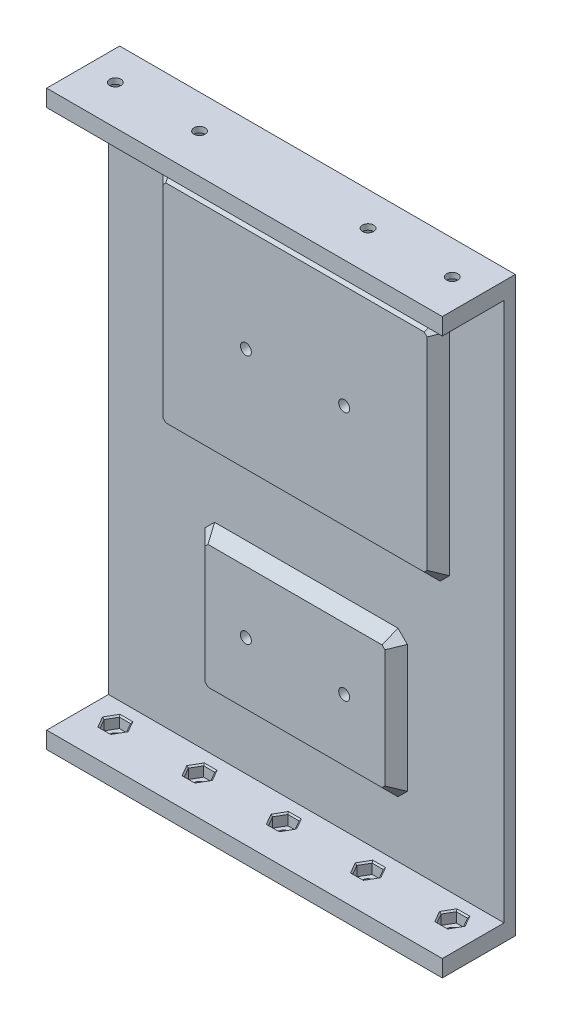
SolidWorks part; units mm, degrees
ref_plane "Front Plane" through (0, 0, 0) normal (0, 0, 1) x (1, 0, 0)
ref_plane "Top Plane" through (0, 0, 0) normal (0, 1, 0) x (1, 0, 0)
ref_plane "Right Plane" through (0, 0, 0) normal (1, 0, 0) x (0, 0, -1)
sketch "Sketch1" plane through (0, 0, 0) normal (0, 0, 1) x (1, 0, 0)
  line L1 (-70.45, -102) -> (70.45, -102)
  line L2 (-70.45, -102) -> (-70.45, 102)
  line L3 (-70.45, 102) -> (70.45, 102)
  line L4 (70.45, -102) -> (70.45, 102)
  line L5 (-70.45, -102) -> (70.45, 102) construction
  line L6 (-70.45, 102) -> (70.45, -102) construction
  point P0 (0, 0)
  dimension "D1" = 140.9
  dimension "D2" = 204
extrude "Boss-Extrude1" add sketch "Sketch1" against normal blind 4
sketch "Sketch4" plane through (0, 0, 0) normal (0, 0, 1) x (1, 0, 0)
  line L0 (70.45, -102) -> (70.45, 102) construction
  line L1 (-70.45, 102) -> (70.45, 102)
  line L2 (-70.45, 102) -> (-70.45, 96)
  line L3 (-70.45, 96) -> (70.45, 96)
  line L4 (70.45, 102) -> (70.45, 96)
  line L6 (-70.45, -102) -> (70.45, -102)
  line L7 (-70.45, -102) -> (-70.45, -96)
  line L8 (-70.45, -96) -> (70.45, -96)
  line L9 (70.45, -102) -> (70.45, -96)
  dimension "D1" = 6
  dimension "D2" = 6
extrude "Boss-Extrude3" add sketch "Sketch4" along normal blind 22
sketch "Sketch5" plane through (0, 102, 0) normal (0, 1, 0) x (1, 0, 0)
  line L0 (-999.5545, -8) -> (49000.4455, -8) construction
  line L1 (70.45, 4) -> (-70.45, 4) construction
  line L2 (0, -14.3) -> (0, 14.3) construction
  circle A0 centre (-30, -8) radius 2
  circle A1 centre (-60, -8) radius 2
  circle A4 centre (60, -8) radius 2
  circle A5 centre (30, -8) radius 2
  dimension "D2" = 4
  dimension "D1" = 12
  dimension "D3" = 30
  dimension "D4" = 60
extrude "Cut-Extrude1" cut sketch "Sketch5" against normal through all both and the other way through all
sketch "Sketch8" plane through (0, -96, 0) normal (0, 1, 0) x (1, 0, 0)
  line L0 (-26.0163, -8) -> (-28.0081, -4.55)
  line L1 (-56.0163, -8) -> (-58.0081, -4.55)
  line L2 (-58.0081, -4.55) -> (-61.9919, -4.55)
  line L3 (-61.9919, -4.55) -> (-63.9837, -8)
  line L4 (-63.9837, -8) -> (-61.9919, -11.45)
  line L5 (-61.9919, -11.45) -> (-58.0081, -11.45)
  line L6 (-58.0081, -11.45) -> (-56.0163, -8)
  line L7 (-28.0081, -4.55) -> (-31.9919, -4.55)
  line L8 (-31.9919, -4.55) -> (-33.9837, -8)
  line L9 (-33.9837, -8) -> (-31.9919, -11.45)
  line L10 (-31.9919, -11.45) -> (-28.0081, -11.45)
  line L11 (-28.0081, -11.45) -> (-26.0163, -8)
  line L12 (3.9837, -8) -> (1.9919, -4.55) [skipped]
  line L13 (1.9919, -4.55) -> (-1.9919, -4.55) [skipped]
  line L14 (-1.9919, -4.55) -> (-3.9837, -8) [skipped]
  line L15 (-3.9837, -8) -> (-1.9919, -11.45) [skipped]
  line L16 (-1.9919, -11.45) -> (1.9919, -11.45) [skipped]
  line L17 (1.9919, -11.45) -> (3.9837, -8) [skipped]
  line L18 (33.9837, -8) -> (31.9919, -4.55)
  line L19 (31.9919, -4.55) -> (28.0081, -4.55)
  line L20 (28.0081, -4.55) -> (26.0163, -8)
  line L21 (26.0163, -8) -> (28.0081, -11.45)
  line L22 (28.0081, -11.45) -> (31.9919, -11.45)
  line L23 (31.9919, -11.45) -> (33.9837, -8)
  line L24 (63.9837, -8) -> (61.9919, -4.55)
  line L25 (61.9919, -4.55) -> (58.0081, -4.55)
  line L26 (58.0081, -4.55) -> (56.0163, -8)
  line L27 (56.0163, -8) -> (58.0081, -11.45)
  line L28 (58.0081, -11.45) -> (61.9919, -11.45)
  line L29 (61.9919, -11.45) -> (63.9837, -8)
  line L30 (-56.0163, -8) -> (-26.0163, -8) construction
  circle A0 centre (-60, -8) radius 3.45 construction
  dimension "D1" = 6.9
  dimension "D3" = 30
  dimension "D2" = 5
extrude "Cut-Extrude4" cut sketch "Sketch8" against normal blind 4
mirror "Mirror1" about plane through (0, 0, 0) normal (0, 1, 0) of "Cut-Extrude4"
sketch "Sketch9" plane through (0, -96, 0) normal (0, 1, 0) x (1, 0, 0)
  line L0 (70.45, 4) -> (-70.45, 4) construction
  circle A0 centre (0, -8) radius 2
  dimension "D2" = 4
  dimension "D1" = 12
extrude "Cut-Extrude5" cut sketch "Sketch9" against normal through all
sketch "Sketch10" plane through (0, -96, 0) normal (0, 1, 0) x (1, 0, 0)
  line L1 (1.9919, -4.55) -> (-1.9919, -4.55)
  line L2 (-1.9919, -4.55) -> (-3.9837, -8)
  line L3 (-3.9837, -8) -> (-1.9919, -11.45)
  line L4 (-1.9919, -11.45) -> (1.9919, -11.45)
  line L5 (1.9919, -11.45) -> (3.9837, -8)
  line L6 (3.9837, -8) -> (1.9919, -4.55)
  circle A0 centre (0, -8) radius 3.45 construction
  dimension "D1" = 6.9
extrude "Cut-Extrude6" cut sketch "Sketch10" against normal up to surface (4 mm away) up to face at (-30, -100, 8)
chamfer "Chamfer1" distance 0.5 angle 45 54 edges at (60, 96, 11.45) (57.0122, 96, 9.725) (57.0122, 96, 6.275) (60, 96, 4.55) (62.9878, 96, 6.275) (62.9878, 96, 9.725) (30, 96, 11.45) (27.0122, 96, 9.725) (27.0122, 96, 6.275) (30, 96, 4.55) (32.9878, 96, 6.275) (32.9878, 96, 9.725) (-30, 96, 11.45) (-32.9878, 96, 9.725) (-32.9878, 96, 6.275) (-30, 96, 4.55) (-27.0122, 96, 6.275) (-27.0122, 96, 9.725) (-60, 96, 11.45) (-62.9878, 96, 9.725) (-62.9878, 96, 6.275) (-60, 96, 4.55) (-57.0122, 96, 6.275) (-57.0122, 96, 9.725) (60, -96, 4.55) (57.0122, -96, 6.275) (57.0122, -96, 9.725) (60, -96, 11.45) (62.9878, -96, 9.725) (62.9878, -96, 6.275) (30, -96, 4.55) (27.0122, -96, 6.275) (27.0122, -96, 9.725) (30, -96, 11.45) (32.9878, -96, 9.725) (32.9878, -96, 6.275) (-2.9878, -96, 6.275) (-2.9878, -96, 9.725) (0, -96, 11.45) (2.9878, -96, 9.725) (2.9878, -96, 6.275) (0, -96, 4.55) (-30, -96, 4.55) (-32.9878, -96, 6.275) (-32.9878, -96, 9.725) (-30, -96, 11.45) (-27.0122, -96, 9.725) (-27.0122, -96, 6.275) (-60, -96, 4.55) (-62.9878, -96, 6.275) (-62.9878, -96, 9.725) (-60, -96, 11.45) (-57.0122, -96, 9.725) (-57.0122, -96, 6.275)
sketch "Sketch11" plane through (0, 0, 0) normal (0, 0, 1) x (1, 0, 0)
  line L1 (-32, -28) -> (32, -28)
  line L2 (-32, -28) -> (-32, -72)
  line L3 (-32, -72) -> (32, -72)
  line L4 (32, -28) -> (32, -72)
  line L5 (-47, 76) -> (47, 76)
  line L6 (-47, 76) -> (-47, 2)
  line L7 (-47, 2) -> (47, 2)
  line L8 (47, 76) -> (47, 2)
  line L11 (-70.45, 96) -> (70.45, 96) construction
  point P8 (0, 76)
  point P10 (0, -72)
  dimension "D1" = 64
  dimension "D2" = 44
  dimension "D3" = 94
  dimension "D4" = 74
  dimension "D5" = 30
  dimension "D6" = 20
extrude "Boss-Extrude4" add sketch "Sketch11" along normal blind 4
chamfer "Chamfer2" distance 1 angle 45 8 edges at (32, -28, 2) (-32, -28, 2) (-32, -72, 2) (-47, 76, 2) (-47, 2, 2) (47, 2, 2) (47, 76, 2) (32, -72, 2)
chamfer "Chamfer3" distance 4 angle 45 16 edges at (-46.5, 2.5, 0) (0, 2, 0) (46.5, 2.5, 0) (47, 39, 0) (46.5, 75.5, 0) (0, 76, 0) (-46.5, 75.5, 0) (-47, 39, 0) (-31.5, -71.5, 0) (0, -72, 0) (31.5, -71.5, 0) (32, -50, 0) (31.5, -28.5, 0) (0, -28, 0) (-31.5, -28.5, 0) (-32, -50, 0)
sketch "Sketch12" plane through (0, 0, 4) normal (0, 0, 1) x (1, 0, 0)
  line L0 (-32, -29) -> (-32, -71) construction
  line L1 (-47, 75) -> (-47, 3) construction
  circle A0 centre (-17.5, 39) radius 1.95
  circle A1 centre (17.5, 39) radius 1.95
  circle A2 centre (-17.5, -50) radius 1.95
  circle A3 centre (17.5, -50) radius 1.95
  point P15 (-32, -50)
  point P18 (-47, 39)
  dimension "D1" = 3.9
  dimension "D2" = 17.5
  dimension "D3" = 35
extrude "Cut-Extrude7" cut sketch "Sketch12" against normal blind 5
